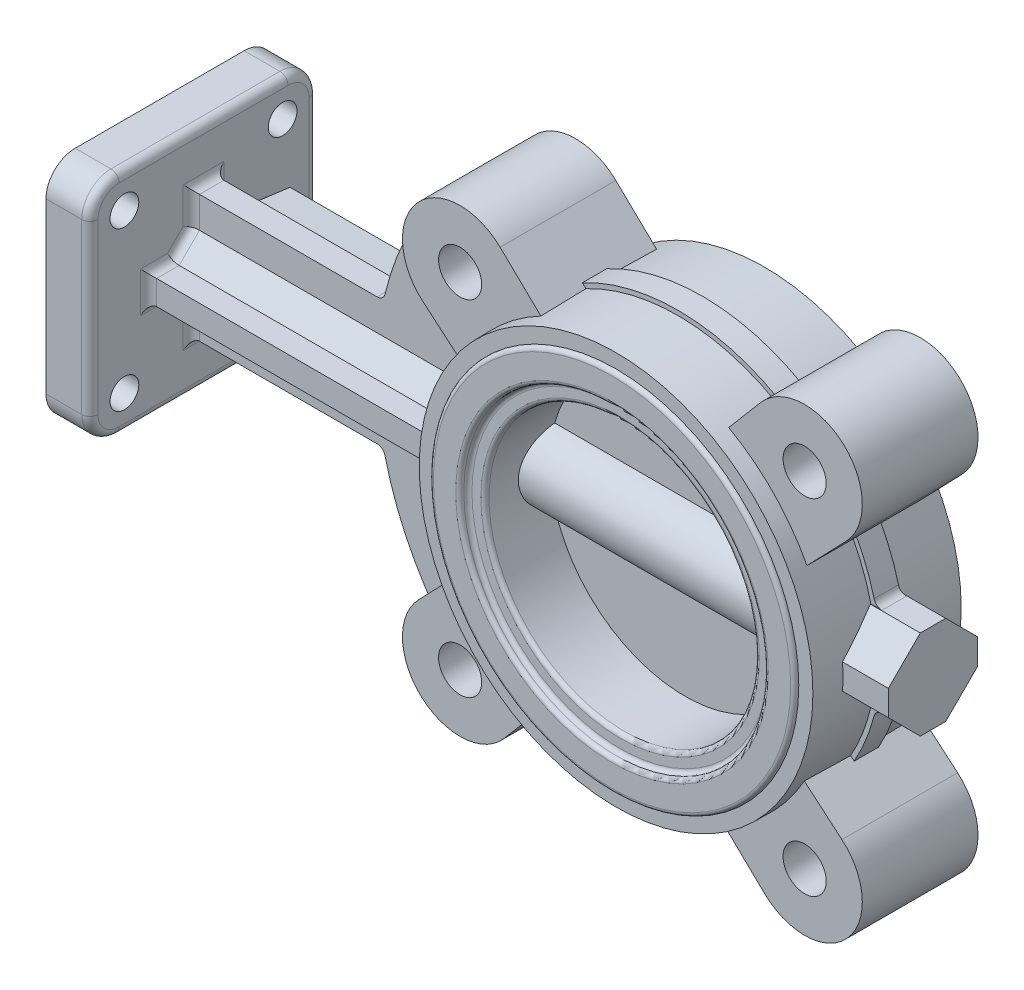
SolidWorks part; units mm, degrees
material "A36"
ref_plane "Front Plane" through (0, 0, 0) normal (0, 0, 1) x (1, 0, 0)
ref_plane "Top Plane" through (0, 0, 0) normal (0, 1, 0) x (1, 0, 0)
ref_plane "Right Plane" through (0, 0, 0) normal (1, 0, 0) x (0, 0, -1)
sketch "Sketch1" plane through (0, 0, 0) normal (0, 0, 1) x (1, 0, 0)
  circle A0 centre (0, 0) radius 61.976
  dimension "D1" = 123.952
extrude "Boss-Extrude1" add sketch "Sketch1" along normal mid plane 46.3931 draft 1
sketch "Sketch2" plane through (0, 0, 23.1965) normal (0, 0, 1) x (1, 0, 0)
  circle A0 centre (0, 0) radius 57.15
  dimension "D1" = 114.3
extrude "Boss-Extrude2" add sketch "Sketch2" along normal blind 1.27
sketch "Sketch3" plane through (0, 0, -23.1965) normal (0, 0, -1) x (-1, 0, 0)
  circle A0 centre (0, 0) radius 57.15
  dimension "D1" = 114.3
extrude "Boss-Extrude3" add sketch "Sketch3" along normal blind 1.27
sketch "Sketch4" plane through (0, 0, -24.4666) normal (0, 0, -1) x (-1, 0, 0)
  circle A0 centre (0, 0) radius 47.625
  dimension "D1" = 95.25
extrude "Cut-Extrude1" cut sketch "Sketch4" against normal blind 2.54
sketch "Sketch5" plane through (0, 0, 24.4666) normal (0, 0, 1) x (1, 0, 0)
  circle A0 centre (0, 0) radius 47.625
  dimension "D1" = 95.25
extrude "Cut-Extrude2" cut sketch "Sketch5" against normal blind 2.54
sketch "Sketch6" plane through (0, 0, 21.9265) normal (0, 0, 1) x (1, 0, 0)
  circle A0 centre (0, 0) radius 42.291
  dimension "D1" = 84.582
extrude "Cut-Extrude3" cut sketch "Sketch6" against normal through all
sketch "Sketch7" plane through (0, 0, 0) normal (0, 1, 0) x (1, 0, 0)
  line L1 (-63.3491, 3.81) -> (-56.9991, 3.81)
  line L2 (-63.3491, 3.81) -> (-63.3491, -3.81)
  line L3 (-63.3491, -3.81) -> (-56.9991, -3.81)
  line L4 (-56.9991, 3.81) -> (-56.9991, -3.81)
  line L5 (-63.3491, 0) -> (-61.976, 0) construction
  line L7 (0, 0) -> (0, 23.1965) construction
  line L8 (61.5711, 23.1965) -> (-61.5711, 23.1965) construction
  dimension "D1" = 7.62
  dimension "D2" = 1.778
  dimension "D3" = 6.35
revolve "Revolve1" add sketch "Sketch7" angle 360 about L7
ref_plane "Plane1" through (57.15, 0, 0) normal (1, 0, 0) x (0, 0, -1)
sketch "Sketch8" plane through (57.15, 0, 0) normal (1, 0, 0) x (0, 0, -1)
  line L1 (-13.97, 13.97) -> (13.97, 13.97)
  line L2 (-13.97, 13.97) -> (-13.97, -13.97)
  line L3 (-13.97, -13.97) -> (13.97, -13.97)
  line L4 (13.97, 13.97) -> (13.97, -13.97)
  line L5 (-13.97, 13.97) -> (13.97, -13.97) construction
  line L6 (-13.97, -13.97) -> (13.97, 13.97) construction
  point P0 (0, 0)
  dimension "D1" = 27.94
extrude "Boss-Extrude4" add sketch "Sketch8" along normal blind 18.796
chamfer "Chamfer1" distance 10 angle 45 4 edges at (68.0383, 13.97, -13.97) (68.0383, -13.97, -13.97) (68.0383, -13.97, 13.97) (68.0383, 13.97, 13.97)
ref_plane "Plane2" through (-63.3491, 0, 0) normal (-1, 0, 0) x (0, 0, 1)
sketch "Sketch9" plane through (-63.3491, 0, 0) normal (-1, 0, 0) x (0, 0, 1)
  line L0 (-3.81, 63.3491) -> (-3.81, -63.3491) construction
  line L1 (-17.2212, 3.81) -> (-3.81, 3.81)
  line L2 (-17.2212, 3.81) -> (-17.2212, -3.81)
  line L3 (-17.2212, -3.81) -> (-3.81, -3.81)
  line L4 (17.2212, 3.81) -> (17.2212, -3.81)
  line L5 (-17.2212, 3.81) -> (17.2212, -3.81) construction
  line L6 (-17.2212, -3.81) -> (17.2212, 3.81) construction
  line L7 (-3.81, -19.9009) -> (3.81, -19.9009)
  line L8 (-3.81, -19.9009) -> (-3.81, -3.81)
  line L9 (-3.81, 19.9009) -> (3.81, 19.9009)
  line L10 (3.81, -19.9009) -> (3.81, -3.81)
  line L11 (-3.81, -19.9009) -> (3.81, 19.9009) construction
  line L12 (-3.81, 19.9009) -> (3.81, -19.9009) construction
  line L13 (3.81, 3.81) -> (17.2212, 3.81)
  line L14 (-3.81, 3.81) -> (-3.81, 19.9009)
  line L15 (3.81, 3.81) -> (3.81, 19.9009)
  line L19 (3.81, -3.81) -> (17.2212, -3.81)
  point P0 (0, 0)
  point P5 (0, 0)
  dimension "D1" = 34.4424
  dimension "D2" = 39.8018
extrude "Boss-Extrude5" add sketch "Sketch9" along normal blind 88.9 and the other way blind 12.7
sketch "Sketch10" plane through (0, 0, -3.81) normal (0, 0, -1) x (-1, 0, 0)
  line L0 (60.142, -19.9009) -> (152.2491, -19.9009) construction
  line L1 (44.7946, 44.7946) -> (66.6362, 66.6362)
  line L2 (0, 0) -> (152.2491, 0) construction
  line L3 (44.7946, -44.7946) -> (66.6362, -66.6362)
  line L4 (44.7946, 44.7946) -> (0, 0) construction
  line L7 (60.142, 19.9009) -> (152.2491, 19.9009) construction
  line L8 (60.142, -19.9009) -> (92.1125, -19.9009)
  line L9 (60.142, 19.9009) -> (92.1125, 19.9009)
  line L10 (0, 0) -> (44.7946, -44.7946) construction
  line L11 (152.2491, 3.81) -> (152.2491, -3.81) construction
  arc A0 (66.6362, -66.6362) -> (92.1125, -19.9009) centre (0, 0) ccw
  arc A1 (-61.7895, -13.97) -> (60.142, -19.9009) centre (0, 0) ccw construction
  arc A2 (60.142, 19.9009) -> (-61.7895, 13.97) centre (0, 0) ccw construction
  arc A3 (44.7946, -44.7946) -> (60.142, -19.9009) centre (0, 0) ccw
  arc A4 (60.142, 19.9009) -> (44.7946, 44.7946) centre (0, 0) ccw
  arc A5 (92.1125, 19.9009) -> (66.6362, 66.6362) centre (0, 0) ccw
  dimension "D1" = 188.4756
  dimension "D2" = 45
  dimension "D3" = 90
extrude "Boss-Extrude6" add sketch "Sketch10" against normal up to surface (7.62 mm away)
sketch "Sketch11" plane through (-152.2491, 0, 0) normal (-1, 0, 0) x (0, 0, 1)
  line L1 (35.56, 35.56) -> (-35.56, 35.56)
  line L2 (35.56, 35.56) -> (35.56, -35.56)
  line L3 (35.56, -35.56) -> (-35.56, -35.56)
  line L4 (-35.56, 35.56) -> (-35.56, -35.56)
  line L5 (35.56, 35.56) -> (-35.56, -35.56) construction
  line L6 (35.56, -35.56) -> (-35.56, 35.56) construction
  point P0 (0, 0)
  dimension "D1" = 71.12
extrude "Boss-Extrude7" add sketch "Sketch11" along normal blind 13.716
chamfer "Chamfer2" distance 6.35 angle 45 2 edges at (-107.0206, 3.81, 3.81) (-107.0206, -3.81, 3.81)
fillet "Fillet1" radius 9.144 4 edges at (-159.1071, 35.56, -35.56) (-159.1071, 35.56, 35.56) (-159.1071, -35.56, -35.56) (-159.1071, -35.56, 35.56)
sketch "Sketch12" plane through (0, 0, -3.81) normal (0, 0, -1) x (-1, 0, 0)
  line L0 (152.2491, 26.416) -> (152.2491, -26.416) construction
  line L1 (143.3591, 15.875) -> (86.2091, 15.875)
  line L2 (143.3591, 15.875) -> (143.3591, -15.875)
  line L3 (143.3591, -15.875) -> (86.2091, -15.875)
  line L4 (86.2091, 15.875) -> (86.2091, -15.875)
  line L5 (143.3591, 15.875) -> (86.2091, -15.875) construction
  line L6 (143.3591, -15.875) -> (86.2091, 15.875) construction
  line L7 (114.7841, 0) -> (0, 0) construction
  point P0 (114.7841, 0)
  dimension "D1" = 57.15
  dimension "D2" = 31.75
  dimension "D3" = 8.89
extrude "Boss-Extrude8" add sketch "Sketch12" along normal up to surface (13.4112 mm away) draft 4
fillet "Fillet2" radius 1.27 7 edges at (47.625, 0, 21.9265) (42.291, 0, 21.9265) (-42.291, 0, -21.9265) (57.15, 0, 24.4666) (47.625, 0, 24.4666) (-57.15, 0, -24.4666) (-47.625, 0, -24.4666)
fillet "Fillet3" radius 2.54 30 edges at (-152.2491, 0, 17.2212) (-152.2491, -3.81, 13.6906) (-152.2491, -6.985, 6.985) (-152.2491, -15.0305, 3.81) (-152.2491, -19.9009, 0) (-152.2491, -15.0305, -3.81) (-152.2491, -6.985, -6.985) (-152.2491, -3.81, -13.6906) (-152.2491, 0, -17.2212) (-152.2491, 3.81, -13.6906) (-152.2491, 6.985, -6.985) (-152.2491, 15.0305, -3.81) (-152.2491, 19.9009, 0) (-152.2491, 15.0305, 3.81) (-152.2491, 6.985, 6.985) (-152.2491, 3.81, 13.6906) (61.7895, 13.97, 0) (61.7895, -13.97, 0) (-92.1125, -19.9009, 0) (-92.1125, 19.9009, 0) (-44.7946, -44.7946, 0) (-44.7946, 44.7946, 0) (-152.2491, -32.8818, -32.8818) (-152.2491, -35.56, 0) (-152.2491, -32.8818, 32.8818) (-152.2491, 0, 35.56) (-152.2491, 32.8818, 32.8818) (-152.2491, 35.56, 0) (-152.2491, 32.8818, -32.8818) (-152.2491, 0, -35.56)
sketch "Sketch14" plane through (-165.9651, 0, 0) normal (-1, 0, 0) x (0, 0, 1)
  circle A0 centre (0, 0) radius 9.525
  dimension "D1" = 19.05
extrude "Cut-Extrude5" cut sketch "Sketch14" against normal blind 7.62
hole_wizard "M8 Clearance Hole1" positions "Sketch16" profile "Sketch17" hole size "M8" standard "ANSI Metric"
sketch "Sketch16" plane through (-165.9651, 0, 0) normal (-1, 0, 0) x (0, 0, 1)
  line L1 (-24.7487, 24.7487) -> (24.7487, 24.7487)
  line L2 (-24.7487, 24.7487) -> (-24.7487, -24.7487)
  line L3 (-24.7487, -24.7487) -> (24.7487, -24.7487)
  line L4 (24.7487, 24.7487) -> (24.7487, -24.7487)
  line L5 (0, 0) -> (0, 24.7487)
  line L6 (0, 0) -> (0, -24.7487)
  point P0 (-24.7487, 24.7487)
  point P2 (24.7487, 24.7487)
  point P4 (24.7487, -24.7487)
  point P6 (-24.7487, -24.7487)
  dimension "D1" = 70
sketch "Sketch17" plane through (-165.9651, 24.7487, -24.7487) normal (0, 1, 0) x (0, 0, 1)
  line L0 (0, 0) -> (0, 13.716)
  line L1 (0, 13.716) -> (4.5, 13.716)
  line L2 (4.5, 13.716) -> (4.5, 0)
  line L5 (4.5, 0) -> (0, 0)
  line L11 (0, -6.35) -> (0, 107.95) construction
  dimension "Thru Hole Dia." = 9
  dimension "Thru Hole Depth" = 13.716
sketch "Sketch18" plane through (75.946, 0, 0) normal (1, 0, 0) x (0, 0, -1)
  circle A0 centre (0, 0) radius 11.5
  dimension "D1" = 23
extrude "Boss-Extrude9" add sketch "Sketch18" against normal blind 127
sketch "Sketch19" plane through (-158.3451, 0, 0) normal (-1, 0, 0) x (0, 0, 1)
  circle A0 centre (0, 0) radius 7
  dimension "D1" = 14
extrude "Boss-Extrude10" add sketch "Sketch19" along normal offset from surface (6.62 mm away) 1 up to face at (-165.9651, 0, 9.525)
sketch "Sketch20" plane through (-164.9651, 0, 0) normal (-1, 0, 0) x (0, 0, 1)
  line L0 (0, 7.7782) -> (-7.7782, 0)
  line L5 (0, -7.7782) -> (7.7782, 0)
  line L6 (7.7782, 0) -> (0, 7.7782)
  line L7 (-7.7782, 0) -> (0, -7.7782)
  line L8 (-7.7782, 0) -> (7.7782, 0) construction
  line L9 (0, 7.7782) -> (0, -7.7782) construction
  point P4 (0, 0)
  dimension "D1" = 11
  dimension "D2" = 90
extrude "Boss-Extrude11" add sketch "Sketch20" along normal blind 19
chamfer "Chamfer3" distance 1.5 angle 45 4 edges at (-174.4651, -7.7782, 0) (-174.4651, 0, 7.7782) (-174.4651, 7.7782, 0) (-174.4651, 0, -7.7782)
sketch "Sketch21" plane through (0, 0, 0) normal (0, 0, 1) x (1, 0, 0)
  circle A0 centre (0, 0) radius 42.291
extrude "Boss-Extrude12" add sketch "Sketch21" along normal mid plane 3.33
sketch "Sketch22" plane through (0, 0, 0) normal (0, 0, 1) x (1, 0, 0)
  line L0 (0, 0) -> (-53.8815, 53.8815) construction
  line L1 (0, 0) -> (53.8815, 53.8815) construction
  line L2 (0, 0) -> (53.8815, -53.8815) construction
  line L3 (0, 0) -> (-53.8815, -53.8815) construction
  line L4 (0, 0) -> (-165.9651, 0) construction
  line L5 (-165.9651, -26.416) -> (-165.9651, 26.416) construction
  line L7 (66.8779, 41.3725) -> (54.5463, 28.5605)
  line L8 (40.1326, 65.5583) -> (30.0808, 53.7228)
  arc A8 (66.8779, 41.3725) -> (40.1326, 65.5583) centre (53.8815, 53.8815) ccw
  arc A9 (54.5463, 28.5605) -> (30.0808, 53.7228) centre (0, 0) ccw
  dimension "D1" = 45
  dimension "D2" = 45
  dimension "D3" = 90
  dimension "D4" = 90
  dimension "D5" = 76.2
extrude "Boss-Extrude13" add sketch "Sketch22" along normal mid plane 36.195
pattern_circular "CirPattern1" count 4 over 360 about axis through (0, 0, 0) along (0, 0, 1) of "Boss-Extrude13"
hole_wizard "5/8-11 Tapped Hole1" positions "Sketch23" profile "Sketch24" tap size "5/8-11" standard "ANSI Inch" end condition through all
sketch "Sketch23" plane through (0, 0, 18.0975) normal (0, 0, 1) x (1, 0, 0)
  point P0 (-53.8815, 53.8815)
  point P3 (53.8815, 53.8815)
  point P6 (53.8815, -53.8815)
  point P9 (-53.8815, -53.8815)
sketch "Sketch24" plane through (-53.8815, 53.8815, 18.0975) normal (1, 0, 0) x (0, -1, 0)
  line L0 (0, 0) -> (0, 53.6575)
  line L1 (0, 53.6575) -> (6.7462, 53.6575)
  line L2 (6.7462, 53.6575) -> (6.7462, 0)
  line L5 (6.7462, 0) -> (0, 0)
  line L11 (0, -6.35) -> (0, 107.95) construction
  dimension "Thru Tap Drill Dia." = 13.4925
  dimension "Thru Tap Drill Depth" = 53.6575
cosmetic thread "Hole Thread1" parameters "D2"=15.875
cosmetic thread "Hole Thread2" parameters "D2"=15.875
cosmetic thread "Hole Thread3" parameters "D2"=15.875
cosmetic thread "Hole Thread4" parameters "D2"=15.875
